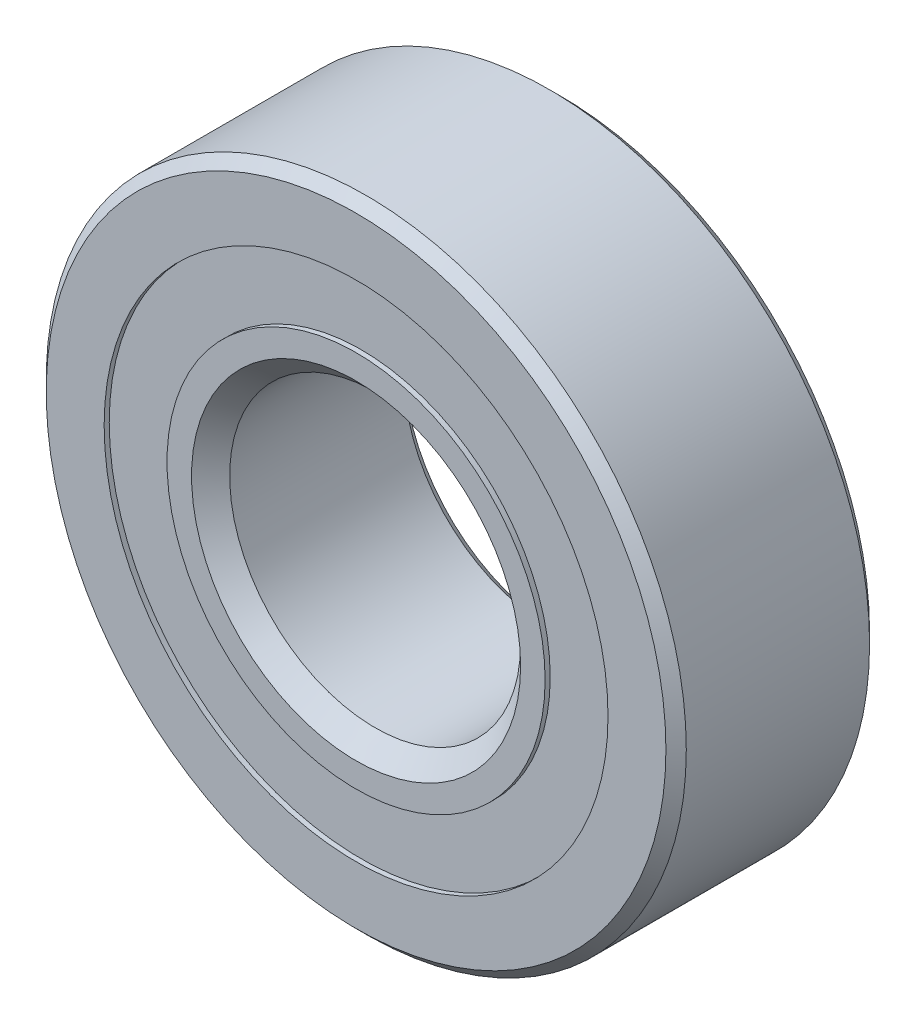
SolidWorks part; units mm, degrees
ref_plane "Front Plane" through (0, 0, 0) normal (0, 0, 1) x (1, 0, 0)
ref_plane "Top Plane" through (0, 0, 0) normal (0, 1, 0) x (1, 0, 0)
ref_plane "Right Plane" through (0, 0, 0) normal (1, 0, 0) x (0, 0, -1)
sketch "Sketch1" plane through (0, 0, 0) normal (1, 0, 0) x (0, 0, -1)
  line L0 (-5.5562, 0) -> (5.5562, 0) construction
  line L1 (0, 17.4625) -> (0, -17.4625) construction
  line L2 (5.0006, 17.4625) -> (-5.0006, 17.4625)
  line L3 (-5.0006, 17.4625) -> (-5.5563, 16.9069)
  line L4 (-5.5563, 16.9069) -> (-5.5563, 13.7467)
  line L5 (-5.5563, 13.7467) -> (-2.4694, 13.7467)
  line L6 (5.5562, 13.7467) -> (2.4694, 13.7467)
  line L7 (5.5562, 16.9069) -> (5.5562, 13.7467)
  line L8 (5.0006, 17.4625) -> (5.5562, 16.9069)
  line L9 (0, 17.4625) -> (0, 12.7) construction
  line L10 (0, 12.7) -> (0, 7.9375) construction
  arc A0 (-2.4694, 13.7467) -> (2.4694, 13.7467) centre (0, 12.7) cw
  point P14 (0, 7.9375)
  dimension "Width" = 11.1125
  dimension "OD" = 34.925
  dimension "D1" = 45
  dimension "D2" = 0.5556
  dimension "D3" = 4.9389
  dimension "D4" = 1.0467
revolve "Revolve1" add sketch "Sketch1" angle 360 about L0
sketch "Sketch2" plane through (0, 0, 0) normal (1, 0, 0) x (0, 0, -1)
  line L0 (-5.2784, 11.6533) -> (-2.4694, 11.6533)
  line L1 (-5.5563, 16.9069) -> (-5.5563, -16.9069) construction
  line L2 (-5.5563, 10.3155) -> (-5.2784, 10.3155) construction
  line L3 (-5.2784, 10.0377) -> (-4.2184, 8.9777)
  line L4 (-4.2184, 8.9777) -> (0, 8.9777)
  line L5 (0, 17.4625) -> (0, -17.4625) construction
  line L6 (0, 8.9777) -> (0, 10.0179)
  line L7 (0, 10.0179) -> (0, 7.9375) construction
  line L8 (-5.5563, 11.6533) -> (-5.5563, 8.9777) construction
  line L9 (-5.5563, 8.9777) -> (-4.2184, 8.9777) construction
  line L10 (-5.2784, 11.6533) -> (-5.2784, 10.0377)
  line L11 (-5.2784, 11.6533) -> (-5.2784, 17.1847) construction
  line L12 (-5.0006, 17.4625) -> (-5.5563, 16.9069) construction
  arc A0 (-2.4694, 11.6533) -> (0, 10.0179) centre (0, 12.7) ccw
  arc A1 (2.4694, 13.7467) -> (-2.4694, 13.7467) centre (0, 12.7) ccw construction
  circle A2 centre (0, 12.7) radius 2.6821 construction
  dimension "D1" = 45
revolve "Revolve2" [suppressed] add sketch "Sketch2" angle 360 about L0
sketch "Sketch3" plane through (0, 0, 0) normal (1, 0, 0) x (0, 0, -1)
  line L0 (-5.2784, 10.0377) -> (-4.2184, 8.9777)
  line L1 (-4.2184, 8.9777) -> (0, 8.9777)
  line L2 (0, 8.9777) -> (0, 10.0179)
  line L3 (-5.5563, 10.3155) -> (-5.5563, 8.9777)
  line L4 (-5.5563, 11.6533) -> (-5.5563, 8.9777) construction
  line L5 (-5.5563, 8.9777) -> (-4.5161, 7.9375)
  line L6 (-4.5161, 7.9375) -> (5.0006, 7.9375)
  line L7 (5.0006, 17.4625) -> (5.0006, -17.4625) construction
  line L8 (5.0006, 7.9375) -> (5.5563, 8.4931)
  line L9 (5.5562, -16.9069) -> (5.5562, 16.9069) construction
  line L10 (5.5563, 8.4931) -> (5.5562, 11.6533)
  line L11 (5.5562, 11.6533) -> (2.4694, 11.6533)
  line L12 (-5.5563, 10.3155) -> (-5.2784, 10.3155)
  line L13 (5.0006, 17.4625) -> (5.5562, 16.9069) construction
  line L14 (-5.2784, 10.3155) -> (-5.2784, 10.0377)
  circle A0 centre (0, 12.7) radius 2.6821 construction
  arc A1 (2.4694, 11.6533) -> (0, 10.0179) centre (0, 12.7) cw
revolve "Revolve3" add sketch "Sketch3" angle 360 about L0
sketch "Sketch4" plane through (0, 0, 0) normal (1, 0, 0) x (0, 0, -1)
  line L0 (-2.6821, 12.7) -> (2.6821, 12.7)
  circle A1 centre (0, 12.7) radius 2.6821 construction
  arc A2 (-2.6821, 12.7) -> (2.6821, 12.7) centre (0, 12.7) cw
  arc A3 (2.4694, 13.7467) -> (-2.4694, 13.7467) centre (0, 12.7) ccw construction
revolve "Revolve4" add sketch "Sketch4" angle 360 about L0
ref_axis "Axis1" through (0, 0, -5.5562) along (0, 0, 1)
pattern_circular "CirPattern1" count 12 every 30 about axis through (0, 0, -5.5562) along (0, 0, 1) of bodies 104
sketch "Sketch5" plane through (0, 0, 0) normal (1, 0, 0) x (0, 0, -1)
  line L0 (-5.5563, 13.7467) -> (-2.4694, 13.7467) construction
  line L1 (-5.2784, 13.7467) -> (-2.6821, 13.7467)
  line L2 (-5.2784, 13.7467) -> (-5.2784, 10.3155)
  line L3 (-5.2784, 10.3155) -> (-2.6821, 10.3155)
  line L4 (-2.6821, 13.7467) -> (-2.6821, 10.3155)
  line L6 (-5.0006, 17.4625) -> (-5.5563, 16.9069) construction
  line L7 (0, 17.4625) -> (0, 7.9375) construction
  line L8 (5.2784, 10.3155) -> (2.6821, 10.3155)
  line L9 (2.6821, 13.7467) -> (2.6821, 10.3155)
  line L10 (5.2784, 13.7467) -> (2.6821, 13.7467)
  line L11 (5.2784, 13.7467) -> (5.2784, 10.3155)
  circle A0 centre (0, 12.7) radius 2.6821 construction
  point P10 (-5.2784, 17.1847)
revolve "Revolve5" add sketch "Sketch5" angle 360 about L0
equation "\"D2@Sketch1\" = \"Width@Sketch1\"*.05"
equation "\"D3@Sketch1\" = \"Width@Sketch1\"/2.25"
equation "\"D4@Sketch1\" = (((\"OD@Sketch1\"-\"Width@Sketch1\")/2)/3.25)/3.5"
equation "\"D2@CirPattern1\" = 360/\"Balls@CirPattern1\""
